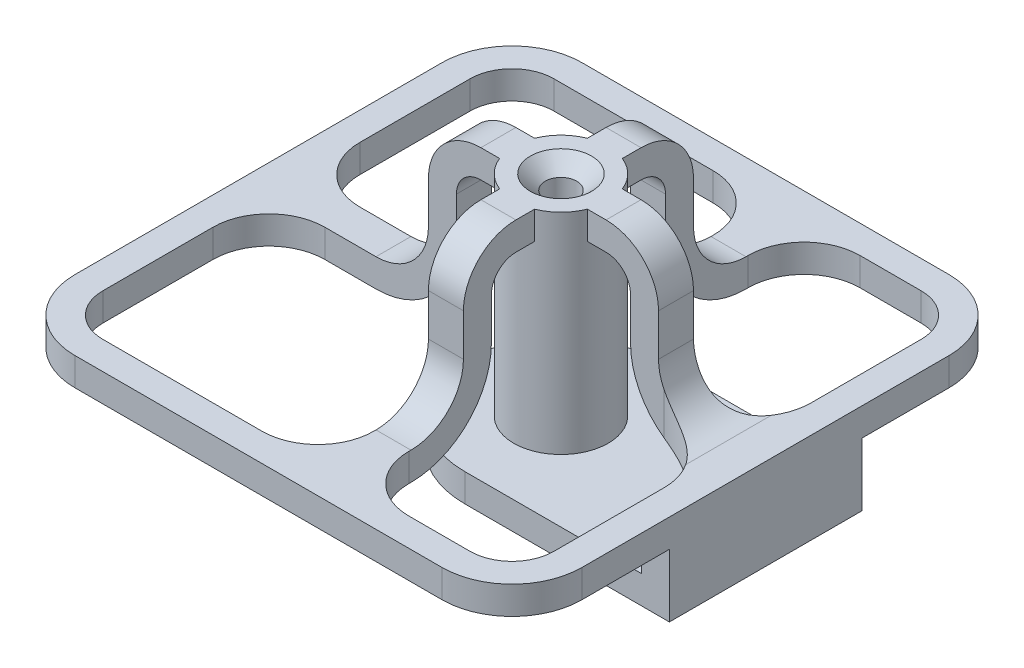
SolidWorks part; units mm, degrees
material "AISI 304"
ref_plane "정면" through (0, 0, 0) normal (0, 0, 1) x (1, 0, 0)
ref_plane "윗면" through (0, 0, 0) normal (0, 1, 0) x (1, 0, 0)
ref_plane "우측면" through (0, 0, 0) normal (1, 0, 0) x (0, 0, -1)
sketch "Sketch1" plane through (0, 0, 0) normal (0, 1, 0) x (1, 0, 0)
  line L0 (0, 0) -> (58.5, 0) construction
  line L1 (0, 27.5) -> (58.5, 27.5)
  line L2 (0, -27.5) -> (58.5, -27.5)
  line L3 (58.5, 27.5) -> (58.5, -27.5)
  arc A0 (0, 27.5) -> (0, -27.5) centre (0, 0) ccw
  point P3 (26.4035, 0)
  dimension "D2" = 27.5
  dimension "D1" = 86
extrude "Boss-Extrude1" add sketch "Sketch1" along normal blind 8
sketch "Sketch2" plane through (58.5, 0, 0) normal (1, 0, 0) x (0, 0, -1)
  line L1 (-27.5, 0) -> (27.5, 0)
  line L2 (-27.5, 0) -> (-27.5, 18)
  line L3 (-27.5, 18) -> (27.5, 18)
  line L4 (27.5, 0) -> (27.5, 18)
  dimension "D1" = 18
extrude "Boss-Extrude2" add sketch "Sketch2" against normal blind 8
sketch "Sketch4" plane through (0, 18, 0) normal (0, 1, 0) x (1, 0, 0)
  line L0 (58.5, 27.5) -> (58.5, -27.5) construction
  line L1 (38.5, 72.5) -> (-66.5, 72.5)
  line L2 (58.5, 52.5) -> (58.5, -52.5)
  line L3 (38.5, -72.5) -> (-66.5, -72.5)
  line L4 (-86.5, 52.5) -> (-86.5, -52.5)
  line L5 (38.5, 64.5) -> (-66.5, 64.5)
  line L6 (-78.5, 52.5) -> (-78.5, -52.5)
  line L7 (38.5, -64.5) -> (-66.5, -64.5)
  line L8 (50.5, 52.5) -> (50.5, -52.5)
  arc A0 (-86.5, -52.5) -> (-66.5, -72.5) centre (-66.5, -52.5) ccw
  arc A1 (38.5, -72.5) -> (58.5, -52.5) centre (38.5, -52.5) ccw
  arc A2 (58.5, 52.5) -> (38.5, 72.5) centre (38.5, 52.5) ccw
  arc A3 (-66.5, 72.5) -> (-86.5, 52.5) centre (-66.5, 52.5) ccw
  arc A4 (-66.5, 64.5) -> (-78.5, 52.5) centre (-66.5, 52.5) ccw
  arc A5 (-78.5, -52.5) -> (-66.5, -64.5) centre (-66.5, -52.5) ccw
  arc A6 (38.5, -64.5) -> (50.5, -52.5) centre (38.5, -52.5) ccw
  arc A7 (50.5, 52.5) -> (38.5, 64.5) centre (38.5, 52.5) ccw
  point P6 (58.5, 0)
  point P7 (58.5, 0)
  point P12 (58.5, -72.5)
  point P15 (58.5, 72.5)
  point P18 (-86.5, 72.5)
  point P31 (0, 0)
  line M17 (58.5, -27.5) -> (58.5, 27.5)
  line M18 (58.5, 27.5) -> (50.5, 27.5)
  line M19 (50.5, 27.5) -> (50.5, -27.5)
  line M20 (50.5, -27.5) -> (58.5, -27.5)
  dimension "D3" = 20
  dimension "D1" = 145
  dimension "D2" = 145
  dimension "D4" = 8
sketch "Sketch3" plane through (0, 8, 0) normal (0, 1, 0) x (1, 0, 0)
  circle A0 centre (0, 0) radius 13.5
  point P2 (0, 0)
  dimension "D1" = 27
extrude "Boss-Extrude3" add sketch "Sketch3" along normal blind 60
extrude "Boss-Extrude4" add sketch "Sketch4" along normal blind 8 contours A7 L8 L2 A2 L1 A3 L4 A0 L3 A1 A6 L7 A5 L6 A4 L5 M18 M20 | M20 M17 M18 M19 region at (51.1921, 18, -65.1921) region at (54.5, 18, 0)
ref_plane "Plane1" through (0, 0, 0) normal (0, 0, 1) x (1, 0, 0)
sketch "Sketch5" plane through (0, 0, 0) normal (0, 0, 1) x (1, 0, 0)
  line L0 (9.8414, 68) -> (17.8893, 68)
  line L1 (32.8893, 53) -> (32.8893, 41)
  line L2 (47.8893, 26) -> (50.5, 26)
  line L3 (13.5, 68) -> (-13.5, 68) construction
  line L4 (9.8414, 60) -> (17.8893, 60)
  line L5 (24.8893, 53) -> (24.8893, 41)
  line L6 (47.8893, 18) -> (50.5, 18)
  line L7 (9.8414, 68) -> (9.8414, 60)
  line L8 (50.5, 26) -> (50.5, 18)
  arc A0 (17.8893, 68) -> (32.8893, 53) centre (17.8893, 53) cw
  arc A1 (32.8893, 41) -> (47.8893, 26) centre (47.8893, 41) ccw
  arc A2 (17.8893, 60) -> (24.8893, 53) centre (17.8893, 53) cw
  arc A3 (24.8893, 41) -> (47.8893, 18) centre (47.8893, 41) ccw
  point P9 (8.5, 53)
  point P12 (8.5, 68)
  point P15 (38.5, 26)
  dimension "D1" = 15
  dimension "D2" = 15
  dimension "D3" = 8
extrude "Boss-Extrude7" add sketch "Sketch5" along normal mid plane 10 separate body contours L5 A3 L6 L8 L2 A1 L1 A0 L0 L7 L4 A2 region at (29.8794, 43.5055, 0)
pattern_circular "CirPattern1" count 4 over 360 about axis through (0, 68, 0) along (0, 1, 0) of "Boss-Extrude7"
sketch "Sketch7" plane through (0, 0, 50.5) normal (0, 0, 1) x (1, 0, 0)
  line L0 (38.5, 18) -> (-66.5, 18) construction
  line L1 (-5, 26) -> (5, 26)
  line L2 (-5, 26) -> (-5, 18)
  line L3 (-5, 18) -> (5, 18)
  line L4 (5, 26) -> (5, 18)
extrude "Boss-Extrude8" add sketch "Sketch7" along normal blind 20
sketch "Sketch8" plane through (9.8414, 0, 0) normal (-1, 0, 0) x (0, 0, 1)
  line L0 (5, 60) -> (-5, 60) construction
  line L1 (-5, 68) -> (5, 68)
  line L2 (-5, 68) -> (-5, 60)
  line L3 (-5, 60) -> (5, 60)
  line L4 (5, 68) -> (5, 60)
extrude "Boss-Extrude9" add sketch "Sketch8" along normal blind 20
sketch "Sketch9" plane through (-50.5, 0, 0) normal (-1, 0, 0) x (0, 0, 1)
  line L0 (-52.5, 18) -> (52.5, 18) construction
  line L1 (-5, 26) -> (5, 26)
  line L2 (-5, 26) -> (-5, 18)
  line L3 (-5, 18) -> (5, 18)
  line L4 (5, 26) -> (5, 18)
  dimension "D1" = 10
extrude "Boss-Extrude10" add sketch "Sketch9" along normal blind 32
sketch "Sketch10" plane through (0, 0, -50.5) normal (0, 0, -1) x (-1, 0, 0)
  line L0 (-38.5, 18) -> (66.5, 18) construction
  line L1 (-5, 26) -> (5, 26)
  line L2 (-5, 26) -> (-5, 18)
  line L3 (-5, 18) -> (5, 18)
  line L4 (5, 26) -> (5, 18)
  dimension "D1" = 10
extrude "Boss-Extrude11" add sketch "Sketch10" along normal blind 15
hole_wizard "CSK for M2 Flat Head Machine Screw1" positions "3DSketch1" profile "Sketch11" countersink size "M2" standard "Ansi Metric" end condition through all
sketch3d "3DSketch1"
  arc A0 (-5, 68, -12.5399) -> (-12.5399, 68, -5) centre (0, 68, 0) ccw construction
  point P0 (0, 0, 0)
  point P3 (0, 68, 0)
  point P6 (0, 0, 0)
  point P10 (0, 81.5, 0)
sketch "Sketch11" plane through (0, 68, 0) normal (1, 0, 0) x (0, 0, 1)
  line L0 (0, 0) -> (0, 68)
  line L1 (0, 68) -> (4.5, 68)
  line L2 (4.5, 68) -> (4.5, 4.1042)
  line L3 (4.5, 4.1042) -> (8.75, 0)
  line L5 (8.75, 0) -> (0, 0)
  line L6 (-4.5, 4.1042) -> (-8.75, 0) construction
  line L11 (0, -6.35) -> (0, 107.95) construction
  dimension "관통 구멍 지름" = 9
  dimension "관통 구멍 깊이" = 68
  dimension "표면 카운터싱크 지름" = 17.5
  dimension "표면 카운터싱크 각도" = 92
fillet "Fillet1" radius 16 8 edges at (-78.5, 22, -5) (-78.5, 22, 5) (-5, 22, 64.5) (5, 22, 64.5) (50.5, 22, 5) (50.5, 22, -5) (5, 22, -64.5) (-5, 22, -64.5)
